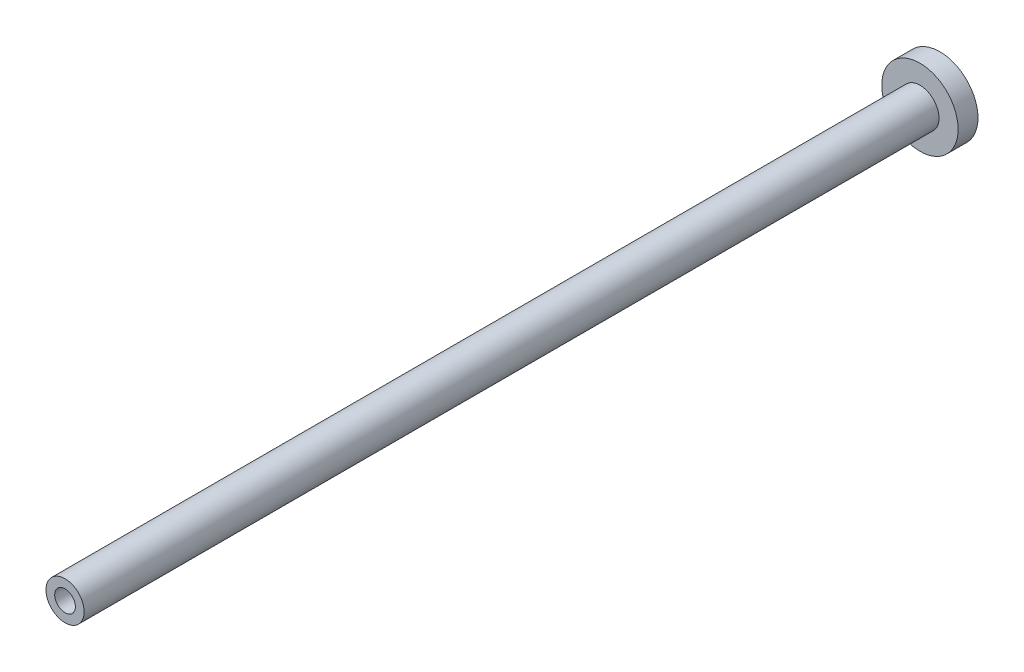
SolidWorks part; units mm, degrees
ref_plane "Front Plane" through (0, 0, 0) normal (0, 0, 1) x (1, 0, 0)
ref_plane "Top Plane" through (0, 0, 0) normal (0, 1, 0) x (1, 0, 0)
ref_plane "Right Plane" through (0, 0, 0) normal (1, 0, 0) x (0, 0, -1)
sketch "Sketch1" plane through (0, 0, 0) normal (0, 0, 1) x (1, 0, 0)
  line L0 (0, -4.8) -> (0, 4.8) construction
  circle A0 centre (0, 0) radius 4.8
  point P6 (0, 0)
  dimension "D2" = 9.6
extrude "Boss-Extrude1" add sketch "Sketch1" along normal blind 110
sketch "Sketch6" plane through (0, 0, 0) normal (0, 0, -1) x (-1, 0, 0)
  circle A0 centre (0, 0) radius 1.25
  dimension "D1" = 2.5
extrude "Boss-Extrude2" add sketch "Sketch6" along normal blind 2.5
sketch "Sketch7" plane through (0, 0, 110) normal (0, 0, 1) x (1, 0, 0)
  circle A0 centre (0, 0) radius 1.3
  dimension "D1" = 2.6
extrude "Cut-Extrude1" cut sketch "Sketch7" against normal blind 2.5
sketch "Sketch9" plane through (0, 0, 110) normal (0, 0, 1) x (1, 0, 0)
  circle A0 centre (0, 0) radius 2.4
  dimension "D1" = 4.8
extrude "Cut-Extrude2" cut sketch "Sketch9" against normal blind 107.5 flip side to cut contours A0
